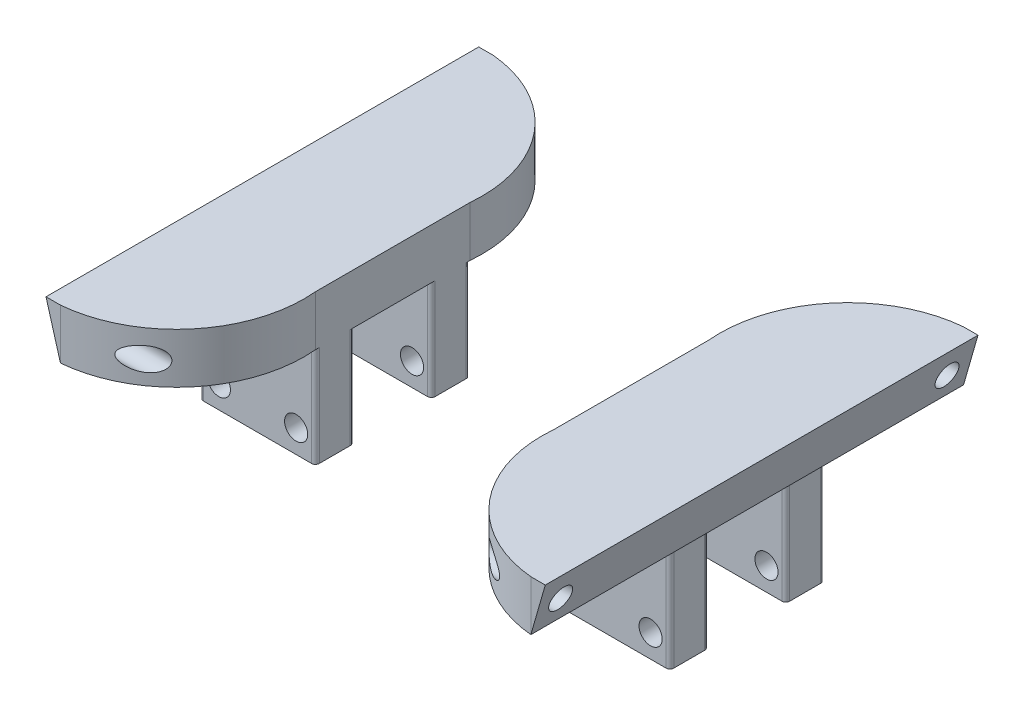
SolidWorks part; units mm, degrees
ref_plane "Front Plane" through (0, 0, 0) normal (0, 0, 1) x (1, 0, 0)
ref_plane "Top Plane" through (0, 0, 0) normal (0, 1, 0) x (1, 0, 0)
ref_plane "Right Plane" through (0, 0, 0) normal (1, 0, 0) x (0, 0, -1)
sketch "Sketch1" plane through (0, 0, 0) normal (0, 0, 1) x (1, 0, 0)
  line L0 (-42.3573, -80) -> (17.3675, -80)
  line L1 (17.3675, -80) -> (19.8113, -71.5)
  line L3 (19.8113, -71.5) -> (-44.8011, -71.5)
  line L5 (-44.8011, -71.5) -> (-42.3573, -80)
extrude "Boss-Extrude1" add sketch "Sketch1" along normal blind 62
sketch "Sketch2" plane through (0, 0, 0) normal (1, 0, 0) x (0, 0, -1)
  line L0 (-62, -80) -> (0, -80) construction
  line L2 (0, -80) -> (0, -71.5) construction
  circle A0 centre (-53, -75) radius 1.5
  circle A1 centre (-3, -75) radius 1.5
  dimension "D1" = 3
  dimension "D2" = 5
  dimension "D3" = 3
  dimension "D4" = 3
  dimension "D5" = 50
extrude "Cut-Extrude1" cut sketch "Sketch2" against normal blind 62 and the other way blind 62
sketch "Sketch3" plane through (0, 0, 0) normal (1, 0, 0) x (0, 0, -1)
  line L1 (-64.0222, -66.0609) -> (-56, -66.0609)
  line L2 (-64.0222, -66.0609) -> (-64.0222, -87.1061)
  line L3 (-64.0222, -87.1061) -> (-56, -87.1061)
  line L4 (-56, -66.0609) -> (-56, -87.1061)
  circle A0 centre (-53, -75) radius 1.5 construction
  dimension "D1" = 3
extrude "Cut-Extrude2" cut sketch "Sketch3" against normal blind 62 and the other way blind 62
sketch "Sketch4" plane through (0, 0, 0) normal (1, 0, 0) x (0, 0, -1)
  line L1 (-58.6301, -78) -> (2.6301, -78)
  line L2 (-58.6301, -78) -> (-58.6301, -84.493)
  line L3 (-58.6301, -84.493) -> (2.6301, -84.493)
  line L4 (2.6301, -78) -> (2.6301, -84.493)
  circle A0 centre (-53, -75) radius 1.5 construction
  dimension "D1" = 3
extrude "Cut-Extrude3" cut sketch "Sketch4" against normal blind 62 and the other way blind 62
sketch "Sketch5" plane through (0, -78, 0) normal (0, -1, 0) x (1, 0, 0)
  line L0 (-42.9323, 56) -> (-42.9323, 0) construction
  line L1 (-42.9323, 33) -> (-18.4949, 33)
  line L2 (-42.9323, 33) -> (-42.9323, 38)
  line L3 (-42.9323, 38) -> (-18.4949, 38)
  line L4 (17.9425, 33) -> (17.9425, 38)
  line L5 (17.9425, 0) -> (17.9425, 56) construction
  line L6 (-12.4949, 56) -> (-12.4949, 0) construction
  line L7 (-42.9323, 23) -> (-18.4949, 23)
  line L8 (-42.9323, 23) -> (-42.9323, 18)
  line L9 (-42.9323, 18) -> (-18.4949, 18)
  line L10 (17.9425, 23) -> (17.9425, 18)
  line L11 (-42.9323, 56) -> (17.9425, 56) construction
  line L12 (-42.9323, 0) -> (17.9425, 0) construction
  line L13 (-6.4949, 38) -> (-6.4949, 33)
  line L14 (-18.4949, 38) -> (-18.4949, 33)
  line L15 (-6.4949, 38) -> (17.9425, 38)
  line L16 (-6.4949, 33) -> (17.9425, 33)
  line L17 (-6.4949, 23) -> (17.9425, 23)
  line L18 (-6.4949, 18) -> (17.9425, 18)
  line L19 (-18.4949, 23) -> (-18.4949, 18)
  line L20 (-6.4949, 23) -> (-6.4949, 18)
  point P12 (17.9425, 28)
  point P13 (-42.9323, 28)
  point P14 (-42.9323, 28)
  dimension "D1" = 5
  dimension "D2" = 5
  dimension "D3" = 10
  dimension "D4" = 5
  dimension "D5" = 5
  dimension "D6" = 6
  dimension "D7" = 6
extrude "Boss-Extrude2" add sketch "Sketch5" along normal blind 13
sketch "Sketch7" plane through (0, 0, 18) normal (0, 0, -1) x (-1, 0, 0)
  line L0 (6.4949, -78) -> (-17.9425, -78) construction
  line L1 (42.9323, -78) -> (-17.9425, -78) construction
  line L2 (-17.9425, -91) -> (-17.9425, -78) construction
  line L3 (42.9323, -91) -> (42.9323, -78) construction
  line L4 (42.9323, -78) -> (18.4949, -78) construction
  line L6 (-2.9425, -94.2351) -> (27.9323, -94.2351)
  line L7 (-2.9425, -94.2351) -> (-2.9425, -78)
  line L8 (-2.9425, -78) -> (27.9323, -78)
  line L9 (27.9323, -94.2351) -> (27.9323, -78)
  circle A0 centre (-15.4425, -88) radius 1.5
  circle A1 centre (-5.4425, -88) radius 1.5
  circle A2 centre (30.4323, -88) radius 1.5
  circle A3 centre (40.4323, -88) radius 1.5
  dimension "D1" = 3
  dimension "D2" = 3
  dimension "D3" = 10
  dimension "D4" = 10
  dimension "D5" = 2.5
  dimension "D6" = 10
  dimension "D7" = 3
  dimension "D8" = 3
  dimension "D9" = 10
  dimension "D10" = 2.5
  dimension "D11" = 10
  dimension "D12" = 10
  dimension "D13" = 2.5
  dimension "D14" = 2.5
extrude "Cut-Extrude4" cut sketch "Sketch7" against normal blind 23
sketch "Sketch8" plane through (0, -78, 0) normal (0, -1, 0) x (1, 0, 0)
  line L0 (-27.9323, 38) -> (-27.9323, 18)
  line L1 (-42.9323, 56) -> (17.9425, 56)
  line L2 (17.9425, 56) -> (17.8889, 55.8874)
  line L3 (2.9425, 38) -> (2.9425, 18)
  line L4 (17.9425, 0) -> (-42.9323, 0)
  line L5 (-42.9323, 0) -> (-42.3916, -0.1309)
  arc A0 (2.9425, 38) -> (17.9425, 56) centre (19.4425, 39.5) cw
  arc A1 (2.9425, 18) -> (17.9425, 0) centre (19.4425, 16.5) ccw
  arc A2 (-27.9323, 18) -> (-42.9323, 0) centre (-44.4323, 16.5) cw
  arc A3 (-27.9323, 38) -> (-42.9323, 56) centre (-44.4323, 39.5) ccw
  line M2 (-27.9323, 38) -> (-27.9323, 33)
  line M6 (-27.9323, 23) -> (-27.9323, 18)
  line M9 (-42.9323, 0) -> (17.9425, 0)
  line M12 (2.9425, 18) -> (2.9425, 23)
  line M16 (2.9425, 33) -> (2.9425, 38)
  line M19 (17.9425, 56) -> (-42.9323, 56)
extrude "Cut-Extrude5" cut sketch "Sketch8" along normal blind 20 and the other way blind 21 contours A3 L0 A2 A1 L3 A0 M2 M6 M9 M12 M16 M19 region at (-12.4949, -78, 28)
fillet "Fillet1" radius 0.5 1 edges at (17.9425, -84.5, 33)
fillet "Fillet2" radius 0.5 1 edges at (17.9425, -84.5, 38)
fillet "Fillet3" radius 0.5 1 edges at (17.9425, -84.5, 23)
fillet "Fillet4" radius 0.5 1 edges at (17.9425, -84.5, 18)
fillet "Fillet5" radius 0.5 1 edges at (2.9425, -84.5, 18)
fillet "Fillet6" radius 0.5 1 edges at (2.9425, -84.5, 33)
fillet "Fillet7" radius 0.5 1 edges at (2.9425, -84.5, 23)
fillet "Fillet8" radius 0.5 1 edges at (2.9425, -84.5, 38)
fillet "Fillet9" radius 0.5 1 edges at (-42.9323, -84.5, 18)
fillet "Fillet10" radius 0.5 1 edges at (-27.9323, -84.5, 18)
fillet "Fillet11" radius 0.5 1 edges at (-27.9323, -84.5, 23)
fillet "Fillet12" radius 0.5 1 edges at (-27.9323, -84.5, 33)
fillet "Fillet13" radius 0.5 1 edges at (-27.9323, -84.5, 38)
fillet "Fillet14" radius 0.5 1 edges
fillet "Fillet15" radius 0.5 1 edges
fillet "Fillet16" radius 0.5 1 edges at (-42.9323, -84.5, 23)
